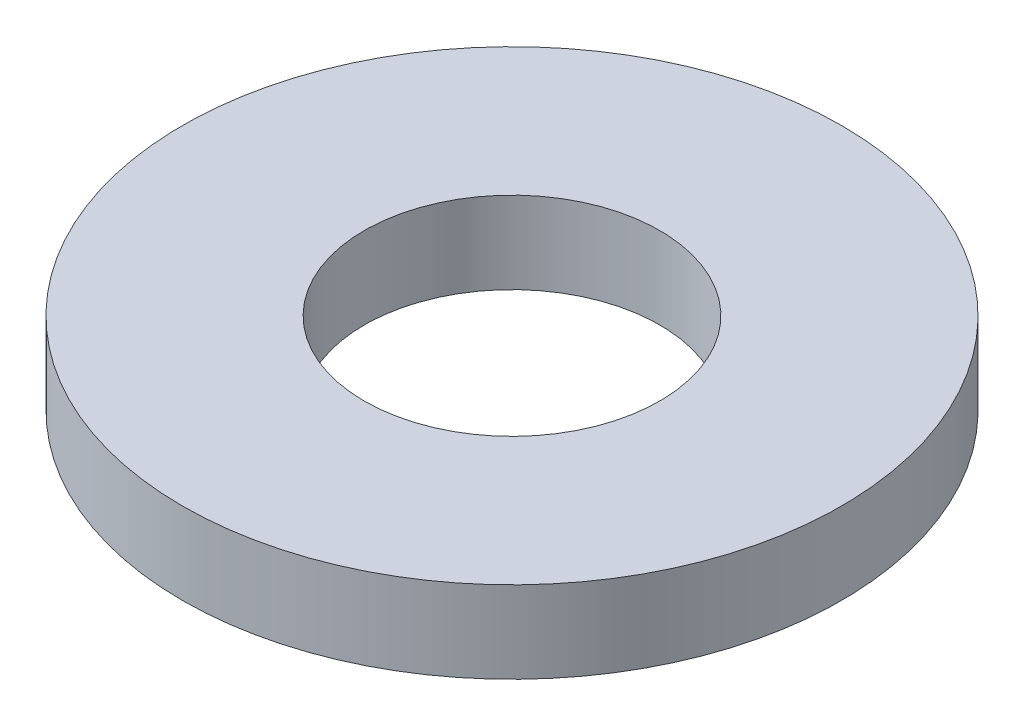
SolidWorks part; units mm, degrees
ref_plane "Front Plane" through (0, 0, 0) normal (0, 0, 1) x (1, 0, 0)
ref_plane "Top Plane" through (0, 0, 0) normal (0, 1, 0) x (1, 0, 0)
ref_plane "Right Plane" through (0, 0, 0) normal (1, 0, 0) x (0, 0, -1)
sketch "Sketch1" plane through (0, 0, 0) normal (0, 1, 0) x (1, 0, 0)
  circle A0 centre (0, 0) radius 72.5
  dimension "FLANGE_OD" = 145
extrude "Boss-Extrude1" add sketch "Sketch1" along normal blind 18
sketch "Sketch2" plane through (0, 0, 0) normal (0, 1, 0) x (1, 0, 0)
  circle A0 centre (0, 0) radius 32.5
  dimension "BORE_D" = 65
extrude "Cut-Extrude1" cut sketch "Sketch2" along normal through all
sketch "Sketch3" plane through (0, 18, 0) normal (0, 1, 0) x (1, 0, 0)
  circle A0 centre (0, 0) radius 24.407 construction
  circle A1 centre (-24.407, 0) radius 6.0772
  dimension "BOLT_D" = 12.1544
  dimension "BOLT_PCD" = 48.8139
extrude "Cut-Extrude2" cut sketch "Sketch3" against normal blind 11.1065 rebuild error yes
pattern_circular "CirPattern1" count 4 over 360 rebuild error yes
